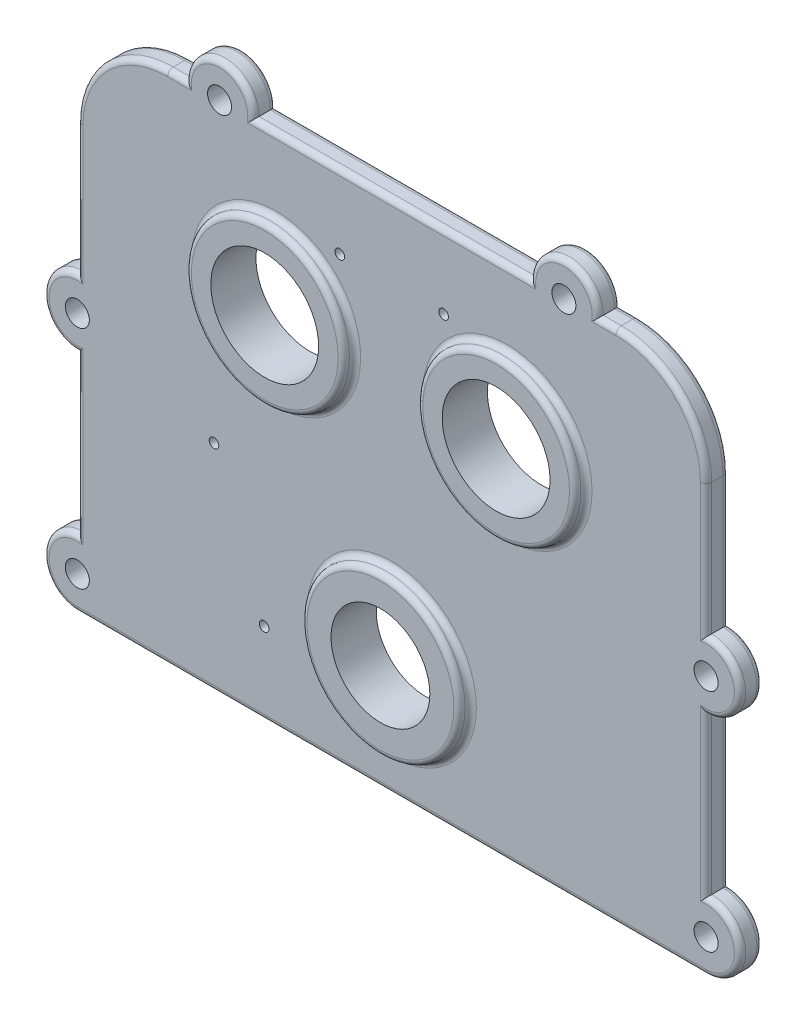
SolidWorks part; units mm, degrees
material "6061 Alloy"
ref_plane "Front Plane" through (0, 0, 0) normal (0, 0, 1) x (1, 0, 0)
ref_plane "Top Plane" through (0, 0, 0) normal (0, 1, 0) x (1, 0, 0)
ref_plane "Right Plane" through (0, 0, 0) normal (1, 0, 0) x (0, 0, -1)
sketch "Sketch1" plane through (0, 0, 0) normal (0, 0, 1) x (1, 0, 0)
  line L0 (-48.4188, 106.7594) -> (48.4187, 106.7594) construction
  line L1 (-88.425, 97.2344) -> (-57.9438, 97.2344)
  line L2 (-88.425, 97.2344) -> (-88.425, 34.8799)
  line L3 (-88.425, -97.2344) -> (88.425, -97.2344)
  line L4 (88.425, 97.2344) -> (88.425, 34.8799)
  line L5 (-88.425, 97.2344) -> (88.425, -97.2344) construction
  line L6 (-88.425, -97.2344) -> (88.425, 97.2344) construction
  line L7 (-38.8938, 97.2344) -> (38.8938, 97.2344)
  line L8 (57.9438, 97.2344) -> (88.425, 97.2344)
  line L9 (-88.425, -47.6701) -> (-88.425, -97.2344)
  line L10 (-88.425, 15.8299) -> (-88.425, -28.6201)
  line L11 (88.425, 15.8299) -> (88.425, -28.6201)
  line L12 (88.425, -47.6701) -> (88.425, -97.2344)
  arc A0 (-38.8938, 97.2344) -> (-57.9438, 97.2344) centre (-48.4188, 97.2344) ccw
  arc A1 (57.9438, 97.2344) -> (38.8938, 97.2344) centre (48.4187, 97.2344) ccw
  arc A2 (-88.425, 34.8799) -> (-88.425, 15.8299) centre (-88.425, 25.3549) ccw
  arc A3 (-88.425, -28.6201) -> (-88.425, -47.6701) centre (-88.425, -38.1451) ccw
  arc A4 (88.425, 15.8299) -> (88.425, 34.8799) centre (88.425, 25.3549) ccw
  arc A5 (88.425, -47.6701) -> (88.425, -28.6201) centre (88.425, -38.1451) ccw
  point P0 (0, 0)
  point P8 (0, 106.7594)
  point P13 (0, 97.2344)
  dimension "D4" = 19.05
  dimension "D5" = 63.5
  dimension "D6" = 9.525
  dimension "D7" = 176.85
  dimension "D1" = 71.8795
  dimension "D2" = 194.4688
  dimension "D3" = 96.8375
extrude "Boss-Extrude1" add sketch "Sketch1" along normal blind 6.35
fillet "Fillet1" radius 25.4 4 edges at (-88.425, -97.2344, 3.175) (88.425, -97.2344, 3.175) (88.425, 97.2344, 3.175) (-88.425, 97.2344, 3.175)
hole_wizard "1/4 Clearance Hole1" positions "Sketch2" profile "Sketch3" hole size "1/4" standard "ANSI Inch"
sketch "Sketch2" plane through (0, 0, 6.35) normal (0, 0, 1) x (1, 0, 0)
  point P0 (-48.4188, 97.2344)
  point P3 (48.4187, 97.2344)
  point P6 (-88.425, 25.3549)
  point P9 (-88.425, -38.1451)
  point P12 (88.425, -38.1451)
  point P15 (88.425, 25.3549)
sketch "Sketch3" plane through (-48.4188, 97.2344, 6.35) normal (1, 0, 0) x (0, -1, 0)
  line L0 (0, 0) -> (0, 27.4298)
  line L1 (0, 27.4298) -> (3.3782, 25.4)
  line L2 (3.3782, 25.4) -> (3.3782, 0)
  line L5 (3.3782, 0) -> (0, 0)
  line L10 (0, 27.4298) -> (-3.3782, 25.4) construction
  line L11 (0, -6.35) -> (0, 107.95) construction
  dimension "Hole Dia." = 6.7564
  dimension "Hole Depth" = 25.4
  dimension "Drill Angle" = 118
sketch "Sketch4" plane through (0, 0, 6.35) normal (0, 0, 1) x (1, 0, 0)
  line L0 (38.8938, 97.2344) -> (-38.8938, 97.2344) construction
  line L1 (-32.5437, 54.3719) -> (32.5437, 54.3719) construction
  circle A0 centre (0, -14.6844) radius 12.7
  circle A1 centre (-32.5437, 54.3719) radius 12.7
  circle A2 centre (32.5437, 54.3719) radius 12.7
  point P5 (0, 97.2344)
  point P8 (0, 54.3719)
  dimension "D1" = 111.9188
  dimension "D2" = 25.4
  dimension "D3" = 42.8625
  dimension "D4" = 25.4
  dimension "D5" = 65.0875
extrude "Cut-Extrude1" cut sketch "Sketch4" against normal through all
sketch "Sketch6" plane through (0, 0, 6.35) normal (0, 0, 1) x (1, 0, 0)
  circle A0 centre (-32.5437, 54.3719) radius 22.225
  circle A1 centre (32.5437, 54.3719) radius 22.225
  circle A2 centre (0, -14.6844) radius 22.225
  circle A3 centre (0, -14.6844) radius 12.7 construction
  circle A4 centre (-32.5437, 54.3719) radius 12.7 construction
  circle A5 centre (32.5437, 54.3719) radius 12.7 construction
  circle A6 centre (0, -14.6844) radius 12.7
  circle A7 centre (32.5437, 54.3719) radius 12.7
  circle A8 centre (-32.5437, 54.3719) radius 12.7
  dimension "D1" = 9.525
  dimension "D2" = 9.525
extrude "Boss-Extrude2" add sketch "Sketch6" along normal blind 3.175 and the other way offset from surface (9.525 mm away) 3.175 other way up to face at (12.7, -14.6844, 0)
fillet "Fillet2" radius 1.5875 12 edges at (54.7688, 54.3719, 9.525) (-10.3187, 54.3719, 9.525) (22.225, -14.6844, 9.525) (22.225, -14.6844, 6.35) (54.7688, 54.3719, 6.35) (-10.3187, 54.3719, 6.35) (54.7688, 54.3719, -3.175) (54.7688, 54.3719, 0) (22.225, -14.6844, 0) (22.225, -14.6844, -3.175) (-10.3187, 54.3719, 0) (-10.3187, 54.3719, -3.175)
fillet "Fillet3" radius 1.5875 30 edges at (60.4844, 97.2344, 0) (80.9855, 89.7949, 0) (-60.4844, 97.2344, 0) (-80.9855, 89.7949, 0) (88.425, 53.3571, 6.35) (60.4844, 97.2344, 6.35) (-60.4844, 97.2344, 6.35) (-88.425, 53.3571, 6.35) (-48.4188, 106.7594, 0) (0, 97.2344, 0) (48.4187, 106.7594, 0) (88.425, 53.3571, 0) (97.95, 25.3549, 0) (88.425, -6.3951, 0) (97.95, -38.1451, 0) (-88.425, -6.3951, 0) (-97.95, -38.1451, 0) (-97.95, 25.3549, 0) (-88.425, 53.3571, 0) (-97.95, 25.3549, 6.35) (-88.425, -6.3951, 6.35) (-97.95, -38.1451, 6.35) (97.95, -38.1451, 6.35) (88.425, -6.3951, 6.35) (97.95, 25.3549, 6.35) (48.4187, 106.7594, 6.35) (80.9855, 89.7949, 6.35) (0, 97.2344, 6.35) (-48.4188, 106.7594, 6.35) (-80.9855, 89.7949, 6.35)
ref_plane "Plane1" through (0, 0, 3.175) normal (0, 0, 1) x (1, 0, 0)
ref_plane "Plane2" through (0, 0, 6.5405) normal (0, 0, 1) x (1, 0, 0)
sketch "Sketch8" plane through (0, 0, 9.525) normal (0, 0, 1) x (1, 0, 0)
  circle A0 centre (-32.5437, 54.3719) radius 15.1638
  circle A1 centre (32.5437, 54.3719) radius 15.1638
  circle A2 centre (0, -14.6844) radius 13.8938
  dimension "D1" = 30.3276
  dimension "D2" = 27.7876
extrude "Cut-Extrude3" cut sketch "Sketch8" against normal through all
sketch "Sketch9" plane through (0, 0, 6.5405) normal (0, 0, 1) x (1, 0, 0)
  line L0 (32.5437, 54.3719) -> (47.7075, 54.3719) construction
  line L1 (-32.5437, 54.3719) -> (-17.3799, 54.3719) construction
  line L2 (48.9775, 54.3719) -> (47.7075, 54.3719)
  line L3 (47.3881, 57.4679) -> (44.2175, 57.4679)
  line L4 (44.2175, 57.4679) -> (44.2175, 51.2759)
  line L5 (44.2175, 51.2759) -> (47.3881, 51.2759)
  line L6 (-16.1099, 54.3719) -> (-17.3799, 54.3719)
  line L7 (-17.6994, 57.4679) -> (-20.87, 57.4679)
  line L8 (-20.87, 57.4679) -> (-20.87, 51.2759)
  line L9 (-20.87, 51.2759) -> (-17.6994, 51.2759)
  circle A0 centre (32.5437, 54.3719) radius 15.1638 construction
  circle A1 centre (-32.5437, 54.3719) radius 15.1638 construction
  circle A2 centre (32.5437, 54.3719) radius 15.1638 construction
  circle A3 centre (-32.5437, 54.3719) radius 15.1638 construction
  arc A8 (47.3881, 51.2759) -> (47.7075, 54.3719) centre (32.5437, 54.3719) ccw construction
  arc A9 (47.3881, 51.2759) -> (47.3881, 57.4679) centre (45.1675, 54.3719) ccw
  arc A10 (47.3881, 57.4679) -> (47.7075, 54.3719) centre (32.5437, 54.3719) cw construction
  arc A11 (-17.6994, 51.2759) -> (-17.3799, 54.3719) centre (-32.5437, 54.3719) ccw construction
  arc A12 (-17.6994, 51.2759) -> (-17.6994, 57.4679) centre (-19.9199, 54.3719) ccw
  arc A13 (-17.6994, 57.4679) -> (-17.3799, 54.3719) centre (-32.5437, 54.3719) cw construction
extrude "Cut-Extrude4" cut sketch "Sketch9" along normal blind 1.905 contours L9 A12 L7 L8 | L5 A9 L3 L4
ref_plane "Plane3" through (0, 0, 5.207) normal (0, 0, 1) x (1, 0, 0)
sketch "Sketch10" plane through (0, 0, 5.207) normal (0, 0, 1) x (1, 0, 0)
  line L0 (0, -14.6844) -> (13.8938, -14.6844) construction
  line L1 (14.6558, -14.6844) -> (13.8938, -14.6844)
  line L2 (13.766, -12.804) -> (10.9469, -12.804)
  line L3 (10.9469, -12.804) -> (10.9469, -16.5647)
  line L4 (10.9469, -16.5647) -> (13.766, -16.5647)
  circle A0 centre (0, -14.6844) radius 13.8938 construction
  circle A1 centre (0, -14.6844) radius 13.8938 construction
  arc A2 (13.766, -16.5647) -> (13.766, -12.804) centre (0, -14.6844) ccw construction
  arc A3 (13.766, -16.5647) -> (13.766, -12.804) centre (12.2242, -14.6844) ccw
extrude "Cut-Extrude5" cut sketch "Sketch10" along normal blind 1.27 contours L3 L4 A3 L2
sketch "Sketch11" plane through (0, 0, 6.35) normal (0, 0, 1) x (1, 0, 0)
  line L0 (-60.8659, 31.449) -> (-14.2154, -26.1898)
  line L1 (3.1636, 61.6238) -> (17.9221, -11.0445)
  line L2 (-32.5437, 54.3719) -> (32.5437, 54.3719) construction
  line L3 (-32.5437, 72.6599) -> (32.5437, 72.6599)
  line L4 (-32.5437, 36.0839) -> (32.5437, 36.0839)
  circle A0 centre (0, -14.6844) radius 18.288
  circle A1 centre (-32.5437, 54.3719) radius 36.4363
  arc A4 (-32.5437, 72.6599) -> (-32.5437, 36.0839) centre (-32.5437, 54.3719) ccw
  arc A5 (32.5437, 36.0839) -> (32.5437, 72.6599) centre (32.5437, 54.3719) ccw
  point P10 (0, 54.3719)
  dimension "D1" = 36.576
  dimension "D2" = 72.8726
hole_wizard "#6-32 Tapped Hole1" positions "Sketch12" profile "Sketch13" tap size "#6-32" standard "ANSI Inch" end condition through all
sketch "Sketch12" plane through (0, 0, 6.35) normal (0, 0, 1) x (1, 0, 0)
  line L0 (-86.8375, 17.5777) -> (-86.8375, -30.368) construction
  line L2 (-56.1959, 95.6469) -> (-63.025, 95.6469) construction
  point P0 (-49.9752, 12.9463)
  point P3 (-35.8775, -24.6589)
  dimension "D1" = 36.8623
  dimension "D2" = 82.7005
  dimension "D3" = 50.96
  dimension "D4" = 37.6052
sketch "Sketch13" plane through (-49.9752, 12.9463, 6.35) normal (1, 0, 0) x (0, -1, 0)
  line L0 (0, 0) -> (0, 9.525)
  line L1 (0, 9.525) -> (1.3525, 9.525)
  line L2 (1.3525, 9.525) -> (1.3525, 0)
  line L5 (1.3525, 0) -> (0, 0)
  line L11 (0, -6.35) -> (0, 107.95) construction
  dimension "Thru Tap Drill Dia." = 2.7051
  dimension "Thru Tap Drill Depth" = 9.525
cosmetic thread "Hole Thread1" parameters "D2"=3.5052
cosmetic thread "Hole Thread2" parameters "D2"=3.5052
sketch "Sketch14" plane through (0, 0, 6.35) normal (0, 0, 1) x (1, 0, 0)
  line L0 (-88.425, -47.6701) -> (88.425, -47.6701)
  line L4 (-88.425, -47.6701) -> (-88.425, -99.5557)
  line L5 (-88.425, -99.5557) -> (88.425, -99.5557)
  line L6 (88.425, -99.5557) -> (88.425, -47.6701)
extrude "Cut-Extrude6" cut sketch "Sketch14" against normal through all
fillet "Fillet4" radius 1.5875 2 edges at (0, -47.6701, 0) (0, -47.6701, 6.35)
sketch "Sketch16" plane through (0, 0, 0) normal (0, 0, -1) x (-1, 0, 0)
  line L0 (32.5437, 72.6599) -> (-32.5437, 72.6599) construction
  line L1 (32.5437, 72.6599) -> (-32.5437, 72.6599)
  arc A0 (-32.5437, 72.6599) -> (-32.5437, 36.0839) centre (-32.5437, 54.3719) ccw construction
  arc A1 (-32.5437, 72.6599) -> (-32.5437, 36.0839) centre (-32.5437, 54.3719) ccw
hole_wizard "#6-32 Tapped Hole2" positions "Sketch19" profile "Sketch20" tap size "#6-32" standard "ANSI Inch" end condition through all
sketch "Sketch19" plane through (0, 0, 0) normal (0, 0, -1) x (-1, 0, 0)
  line L0 (32.5437, 72.6599) -> (-32.5437, 72.6599) construction
  line L1 (-14.605, 76.6223) -> (14.605, 76.6223) construction
  line L3 (40.6416, 95.6469) -> (-40.6416, 95.6469) construction
  point P0 (-14.605, 76.6223)
  point P2 (14.605, 76.6223)
  point P14 (0, 95.6469)
  point P15 (0, 76.6223)
  dimension "D1" = 3.9624
  dimension "D2" = 29.21
sketch "Sketch20" plane through (14.605, 76.6223, 0) normal (1, 0, 0) x (0, 1, 0)
  line L0 (0, 0) -> (0, 9.525)
  line L1 (0, 9.525) -> (1.3525, 9.525)
  line L2 (1.3525, 9.525) -> (1.3525, 0)
  line L5 (1.3525, 0) -> (0, 0)
  line L11 (0, -6.35) -> (0, 107.95) construction
  dimension "Thru Tap Drill Dia." = 2.7051
  dimension "Thru Tap Drill Depth" = 9.525
cosmetic thread "Hole Thread3" parameters "D2"=3.5052
cosmetic thread "Hole Thread4" parameters "D2"=3.5052
